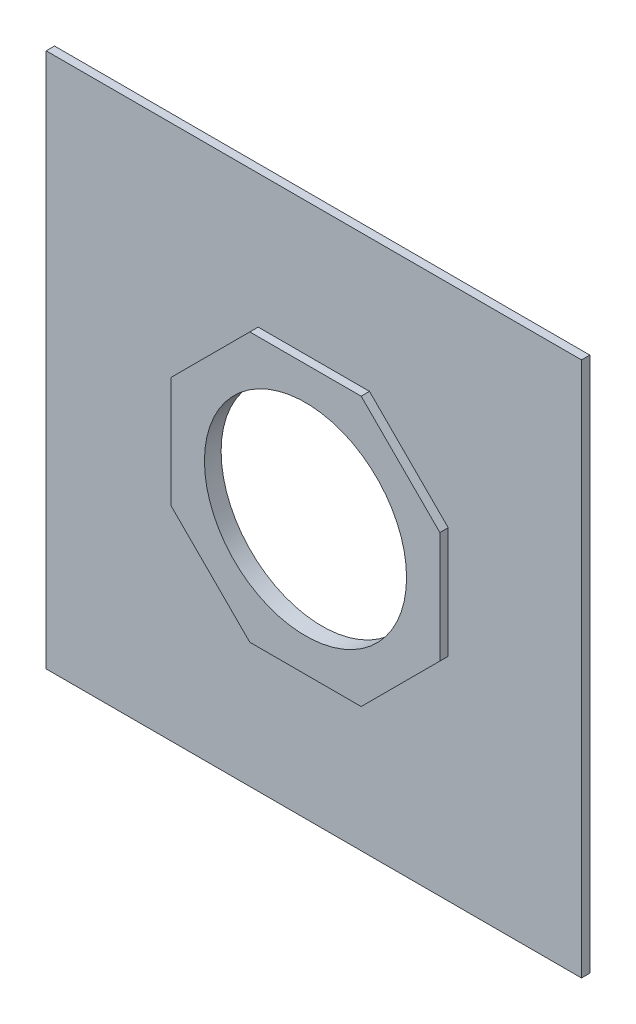
SolidWorks part; units mm, degrees
ref_plane "Front Plane" through (0, 0, 0) normal (0, 0, 1) x (1, 0, 0)
ref_plane "Top Plane" through (0, 0, 0) normal (0, 1, 0) x (1, 0, 0)
ref_plane "Right Plane" through (0, 0, 0) normal (1, 0, 0) x (0, 0, -1)
sketch "Sketch1" plane through (0, 0, 0) normal (0, 0, 1) x (1, 0, 0)
  line L1 (21.2077, 51.2) -> (-21.2077, 51.2)
  line L2 (-21.2077, 51.2) -> (-51.2, 21.2077)
  line L3 (-51.2, 21.2077) -> (-51.2, -21.2077)
  line L4 (-51.2, -21.2077) -> (-21.2077, -51.2)
  line L5 (-21.2077, -51.2) -> (21.2077, -51.2)
  line L6 (21.2077, -51.2) -> (51.2, -21.2077)
  line L7 (51.2, -21.2077) -> (51.2, 21.2077)
  line L8 (51.2, 21.2077) -> (21.2077, 51.2)
  line L9 (101.9739, -101.9739) -> (-101.9739, -101.9739)
  line L10 (101.9739, -101.9739) -> (101.9739, 101.9739)
  line L11 (101.9739, 101.9739) -> (-101.9739, 101.9739)
  line L12 (-101.9739, -101.9739) -> (-101.9739, 101.9739)
  line L13 (101.9739, -101.9739) -> (-101.9739, 101.9739) construction
  line L14 (101.9739, 101.9739) -> (-101.9739, -101.9739) construction
  circle A0 centre (0, 0) radius 38.5
  circle A1 centre (0, 0) radius 51.2 construction
  point P16 (-101.9739, 101.9739)
  dimension "D1" = 77
  dimension "D2" = 12.7
extrude "Boss-Extrude1" add sketch "Sketch1" along normal blind 3.175 contours L7 L8 L1 L2 L3 L4 L5 L6 A0 | L12 L9 L10 L11 L8 L7 L6 L5 L4 L3 L2 L1 region at (35.1799, 35.1799, 0) region at (0, -99.0896, 0)
extrude "Boss-Extrude2" add sketch "Sketch1<3>" along normal blind 6.35 contours L7 L8 L1 L2 L3 L4 L5 L6 A0 region at (35.1799, 35.1799, 0)
sketch "Sketch1<3>" plane through (0, 0, 0) normal (0, 0, 1) x (1, 0, 0) same geometry as "Sketch1"
